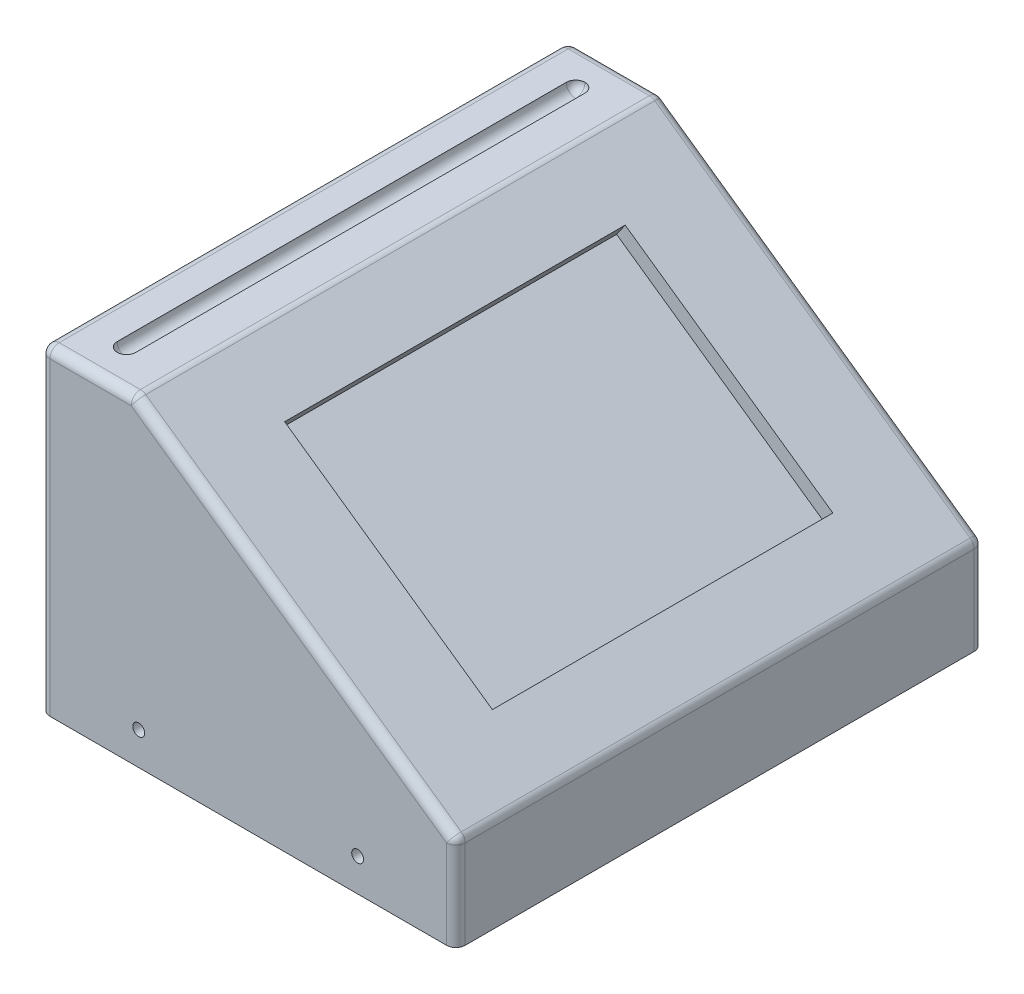
SolidWorks part; units mm, degrees
ref_plane "Front Plane" through (0, 0, 0) normal (0, 0, 1) x (1, 0, 0)
ref_plane "Top Plane" through (0, 0, 0) normal (0, 1, 0) x (1, 0, 0)
ref_plane "Right Plane" through (0, 0, 0) normal (1, 0, 0) x (0, 0, -1)
sketch "Sketch1" plane through (0, 0, 0) normal (0, 0, 1) x (1, 0, 0)
  line L0 (0, 0) -> (0, -50)
  line L1 (0, -50) -> (-222.0219, -50)
  line L2 (0, 0) -> (-172.0219, 120.4511)
  line L3 (-172.0219, 120.4511) -> (-172.0219, -50)
  line L4 (-172.0219, 120.4511) -> (-222.0219, 120.4511)
  line L5 (-222.0219, 120.4511) -> (-222.0219, -50)
  dimension "D1" = 50
  dimension "D2" = 210
  dimension "D3" = 125
  dimension "D4" = 50
extrude "Boss-Extrude1" add sketch "Sketch1" along normal blind 282 contours L4 L5 L1 L3 | L2 L3 L1 L0
sketch "Sketch3" plane through (0, 0, 0) normal (0.5736, 0.8192, 0) x (0.8192, -0.5736, 0)
  line L0 (-210, 0) -> (0, -282)
  line L2 (-172.766, -50) -> (-37.234, -50)
  line L3 (-172.766, -50) -> (-172.766, -232)
  line L4 (-172.766, -232) -> (-37.234, -232)
  line L5 (-37.234, -50) -> (-37.234, -232)
  line L6 (-172.766, -50) -> (-37.234, -232) construction
  line L7 (-172.766, -232) -> (-37.234, -50) construction
  point P4 (-105, -141)
  dimension "D1" = 182
extrude "Cut-Extrude1" cut sketch "Sketch3" against normal blind 8 contours L3 L4 L0 | L5 L2 L0
sketch "Sketch4" plane through (0, 120.4511, 0) normal (0, 1, 0) x (1, 0, 0)
  line L0 (-172.0219, -282) -> (-222.0219, 0)
  line L1 (-172.0219, 0) -> (-222.0219, 0) construction
  line L2 (-222.0219, -282) -> (-222.0219, 0) construction
  line L4 (-202.0219, -266) -> (-192.0219, -266)
  line L5 (-202.0219, -266) -> (-202.0219, -16)
  line L6 (-202.0219, -16) -> (-192.0219, -16)
  line L7 (-192.0219, -266) -> (-192.0219, -16)
  line L8 (-202.0219, -266) -> (-192.0219, -16) construction
  line L9 (-202.0219, -16) -> (-192.0219, -266) construction
  point P7 (-197.0219, -141)
  dimension "D1" = 250
  dimension "D2" = 10
extrude "Cut-Extrude2" cut sketch "Sketch4" against normal blind 5 contours L0 L7 L6 L5 | L4 L7 L0 L5
fillet "Fillet3" radius 5 2 edges at (-192.0219, 115.4511, 141) (-202.0219, 115.4511, 141)
sketch "Sketch5" plane through (0, 0, 282) normal (0, 0, 1) x (1, 0, 0)
  line L0 (0, 0) -> (0, -50) construction
  line L1 (-222.0219, -50) -> (0, -50)
  line L2 (-222.0219, -50) -> (-222.0219, -45)
  line L3 (-222.0219, -45) -> (0, -45)
  line L4 (0, -50) -> (0, -45)
  line L5 (-222.0219, 120.4511) -> (-222.0219, -50) construction
  line L6 (-182.0219, -45) -> (-157.0219, -45)
  line L7 (-182.0219, -45) -> (-182.0219, -20)
  line L8 (-182.0219, -20) -> (-157.0219, -20)
  line L9 (-157.0219, -45) -> (-157.0219, -20)
  line L10 (-40, -45) -> (-65, -45)
  line L11 (-40, -45) -> (-40, -20)
  line L12 (-40, -20) -> (-65, -20)
  line L13 (-65, -45) -> (-65, -20)
  line L14 (-182.0219, -20) -> (-157.0219, -45)
  line L15 (-40, -20) -> (-65, -45)
  circle A0 centre (-52.5, -32.5) radius 3.175
  circle A1 centre (-169.5219, -32.5) radius 3.175
  dimension "D8" = 6.35
  dimension "D9" = 6.35
  dimension "D1" = 5
  dimension "D2" = 40
  dimension "D3" = 25
  dimension "D4" = 25
  dimension "D5" = 40
  dimension "D6" = 25
  dimension "D7" = 25
extrude "Cut-Extrude3" cut sketch "Sketch5" against normal blind 7.7 contours A0 | A1
sketch "Sketch6" plane through (0, 0, 0) normal (0, 0, -1) x (-1, 0, 0)
  circle A1 centre (169.5219, -32.5) radius 3.175
  circle A2 centre (169.5219, -32.5) radius 3.175
  circle A3 centre (52.5, -32.5) radius 3.175
  circle A4 centre (52.5, -32.5) radius 3.175
  dimension "D2" = 0
  dimension "D3" = 0
extrude "Cut-Extrude4" cut sketch "Sketch6" against normal blind 7.7
fillet "Fillet4" radius 5 11 edges at (0, 0, 141) (-172.0219, 120.4511, 141) (-222.0219, 120.4511, 141) (-222.0219, 35.2255, 0) (-222.0219, 35.2255, 282) (-197.0219, 120.4511, 0) (-197.0219, 120.4511, 282) (-86.011, 60.2255, 0) (-86.011, 60.2255, 282) (0, -25, 0) (0, -25, 282)
